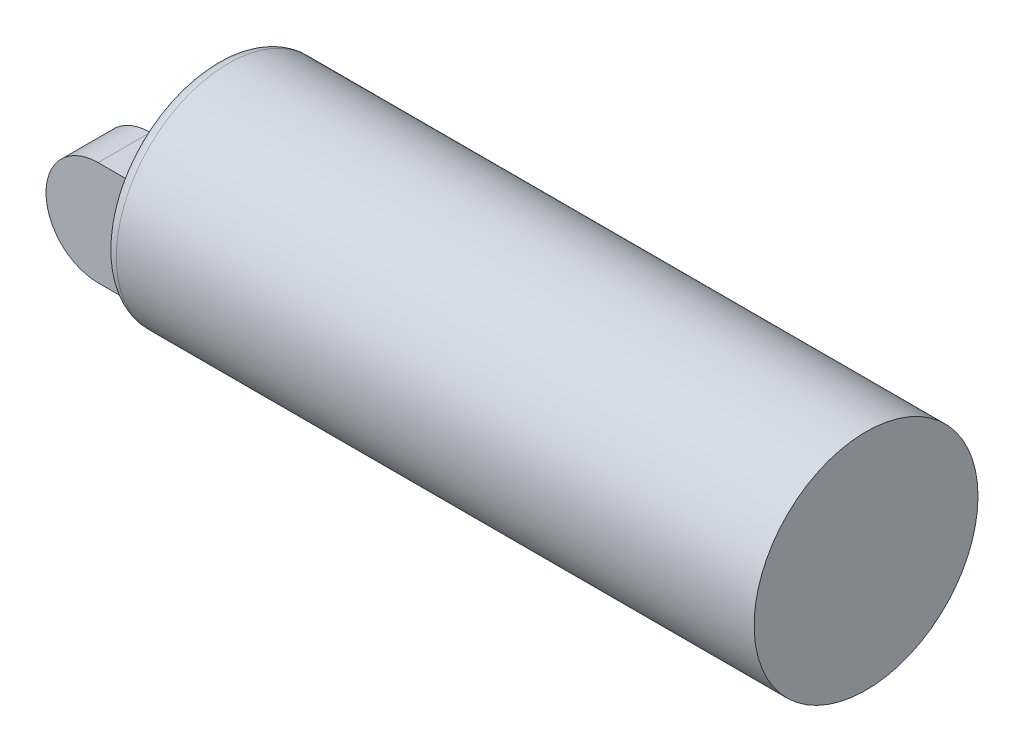
SolidWorks part; units mm, degrees
ref_plane "Plano frontal" through (0, 0, 0) normal (0, 0, 1) x (1, 0, 0)
ref_plane "Plano superior" through (0, 0, 0) normal (0, 1, 0) x (1, 0, 0)
ref_plane "Plano direito" through (0, 0, 0) normal (1, 0, 0) x (0, 0, -1)
sketch "Esboço4" plane through (0, 0, 0) normal (1, 0, 0) x (0, 0, -1)
  circle A0 centre (0, 0) radius 4.3
  dimension "D1" = 8.6
extrude "Ressalto-extrusão1" add sketch "Esboço4" against normal blind 25
sketch "Esboço5" plane through (-25, 0, 0) normal (-1, 0, 0) x (0, 0, 1)
  line L1 (-3.5, -2) -> (3.5, -2)
  line L2 (-3.5, -2) -> (-3.5, 2)
  line L3 (-3.5, 2) -> (3.5, 2)
  line L4 (3.5, -2) -> (3.5, 2)
  line L5 (-3.5, -2) -> (3.5, 2) construction
  line L6 (-3.5, 2) -> (3.5, -2) construction
  point P0 (0, 0)
  dimension "D1" = 7
  dimension "D2" = 4
extrude "Ressalto-extrusão4" add sketch "Esboço5" along normal blind 3 contours L3 L4 L1 L2
sketch "Esboço7" plane through (-28, 0, 0) normal (-1, 0, 0) x (0, 0, 1)
  line L0 (-3.5, 2) -> (3.5, 2) construction
  line L1 (-1.49, -2) -> (1.49, -2)
  line L2 (-1.49, -2) -> (-1.49, 2)
  line L3 (-1.49, 2) -> (1.49, 2)
  line L4 (1.49, -2) -> (1.49, 2)
  line L5 (-1.49, -2) -> (1.49, 2) construction
  line L6 (-1.49, 2) -> (1.49, -2) construction
  point P0 (0, 0)
  dimension "D1" = 2.98
extrude "Corte-extrusão2" cut sketch "Esboço7" against normal blind 3
sketch "Esboço8" plane through (0, 0, -1.49) normal (0, 0, 1) x (1, 0, 0)
  line L0 (-25, 2) -> (-25, -2) construction
  circle A0 centre (-26.63, 0) radius 0.9
  point P0 (-26.63, 0)
  dimension "D2" = 1.8
  dimension "D1" = 1.63
extrude "Corte-extrusão3" cut sketch "Esboço8" against normal blind 2
fillet "Filete2" 2 edges at (-28, -2, -2.495) (-28, 2, -2.495) type full round first side face at (-26.5, -2, -2.495) second side face at (-26.5, 2, -2.495) middle face at (-28, 0, -2.495)
mirror "Espelhar7" about plane through (0, 0, 0) normal (0, 0, 1) of "Corte-extrusão3"
fillet "Filete3" 2 edges at (-28, -2, 2.495) (-28, 2, 2.495) type full round first side face at (-26.5, -2, 2.495) second side face at (-26.5, 2, 2.495) middle face at (-28, 0, 2.495)
fillet "Filete4" radius 0.5 1 edges at (-25, 0, -4.3)
